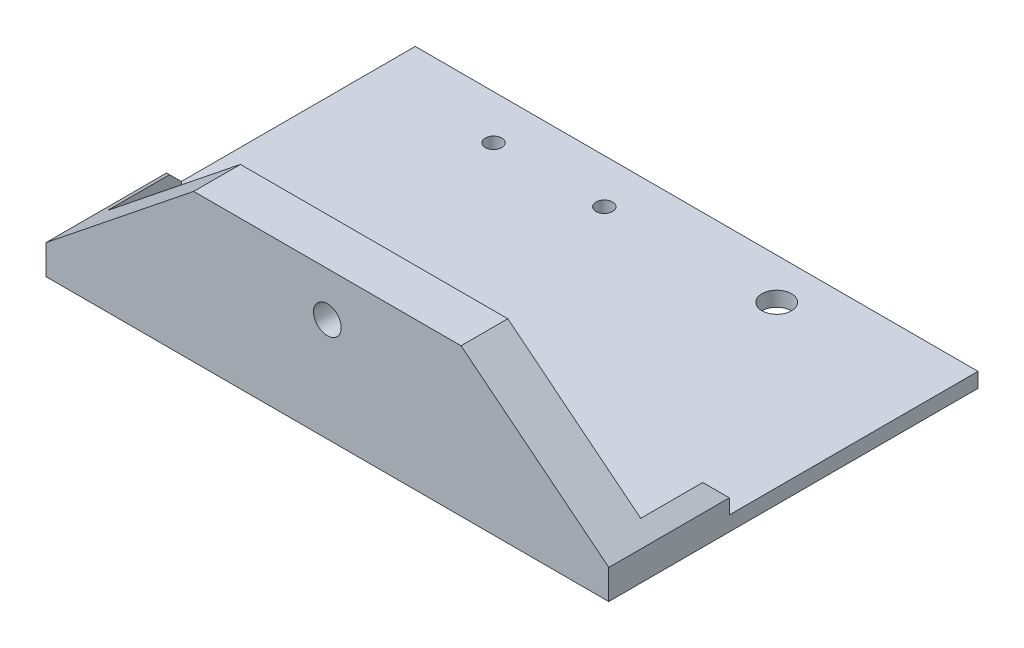
SolidWorks part; units mm, degrees
ref_plane "Front Plane" through (0, 0, 0) normal (0, 0, 1) x (1, 0, 0)
ref_plane "Top Plane" through (0, 0, 0) normal (0, 1, 0) x (1, 0, 0)
ref_plane "Right Plane" through (0, 0, 0) normal (1, 0, 0) x (0, 0, -1)
sketch "Sketch1" plane through (0, 0, 0) normal (0, 1, 0) x (1, 0, 0)
  line L9 (-4.893, 40.3981) -> (64.957, 40.3981)
  line L10 (-4.893, 40.3981) -> (-4.893, -23.1019)
  line L11 (-4.893, -23.1019) -> (64.957, -23.1019)
  line L12 (64.957, 40.3981) -> (64.957, -23.1019)
  circle A0 centre (2.727, 32.7781) radius 1.4224
  circle A2 centre (21.777, 32.7781) radius 1.4224
  circle A3 centre (2.727, 1.0281) radius 1.4224
  circle A4 centre (21.777, 1.0281) radius 1.4224
  circle A5 centre (49.6808, -9.8023) radius 2.54
  circle A6 centre (50.8255, 33.3777) radius 2.54
  point P4 (43.6232, 32.7781)
  point P5 (45.3849, -7.0434)
  point P6 (0, 0)
  point P7 (42.8096, -7.7431)
  point P8 (0, 0)
  point P13 (50.8255, 32.7781)
  point P14 (50.8255, -14.465)
  point P17 (49.6808, -14.8823)
  dimension "D9" = 7.62
  dimension "D10" = 7.62
  dimension "D11" = 2.8448
  dimension "D12" = 2.8448
  dimension "D1" = 5.08
  dimension "D2" = 5.08
  dimension "D13" = 2.8448
  dimension "D14" = 2.8448
  dimension "D3" = 31.75
  dimension "D4" = 19.05
  dimension "D5" = 31.75
  dimension "D6" = 63.5
  dimension "D7" = 69.85
  dimension "D8" = 19.05
  dimension "D15" = 43.18
extrude "Boss-Extrude1" add sketch "Sketch1" along normal blind 2.54 and the other way blind 2.54
sketch "Sketch2" plane through (0, 2.54, 0) normal (0, 1, 0) x (1, 0, 0)
  line L0 (64.957, -23.1019) -> (64.957, 40.3981) construction
  line L2 (-4.893, -23.1019) -> (64.957, -23.1019)
  line L3 (-4.893, -23.1019) -> (-4.893, -15.0633)
  line L4 (-4.893, -15.0633) -> (64.957, -15.0633)
  line L5 (64.957, -23.1019) -> (64.957, -15.0633)
extrude "Boss-Extrude2" add sketch "Sketch2" along normal blind 20.32
sketch "Sketch3" plane through (-4.893, 0, 0) normal (-1, 0, 0) x (0, 0, 1)
  line L0 (15.0633, 15.24) -> (2.3633, 2.54)
  line L6 (-40.3981, -2.54) -> (23.1019, -2.54)
  line L7 (23.1019, -2.54) -> (23.1019, 22.86)
  line L8 (23.1019, 22.86) -> (15.0633, 22.86)
  line L9 (15.0633, 22.86) -> (15.0633, 2.54)
  line L10 (15.0633, 2.54) -> (-40.3981, 2.54)
  line L11 (-40.3981, 2.54) -> (-40.3981, -2.54)
  line L12 (-40.3981, -2.54) -> (23.1019, -2.54)
  line L13 (23.1019, -2.54) -> (23.1019, 22.86)
  line L14 (23.1019, 22.86) -> (15.0633, 22.86)
  line L15 (15.0633, 22.86) -> (15.0633, 15.24)
  line L16 (2.3633, 2.54) -> (-40.3981, 2.54)
  line L17 (-40.3981, 2.54) -> (-40.3981, -2.54)
  dimension "D2" = 12.7
  dimension "D3" = 12.7
  dimension "D1" = 0
extrude "Boss-Extrude3" add sketch "Sketch3" along normal blind 2.54
sketch "Sketch4" plane through (64.957, 0, 0) normal (1, 0, 0) x (0, 0, -1)
  line L0 (-15.0633, 15.24) -> (-2.3633, 2.54) construction
  line L1 (-15.0633, 15.24) -> (-2.3633, 2.54)
  line L6 (-23.1019, -2.54) -> (40.3981, -2.54)
  line L7 (40.3981, -2.54) -> (40.3981, 2.54)
  line L8 (40.3981, 2.54) -> (-15.0633, 2.54)
  line L9 (-15.0633, 2.54) -> (-15.0633, 22.86)
  line L10 (-15.0633, 22.86) -> (-23.1019, 22.86)
  line L11 (-23.1019, 22.86) -> (-23.1019, -2.54)
  line L12 (-23.1019, -2.54) -> (40.3981, -2.54)
  line L13 (40.3981, -2.54) -> (40.3981, 2.54)
  line L14 (40.3981, 2.54) -> (-2.3633, 2.54)
  line L15 (-15.0633, 15.24) -> (-15.0633, 22.86)
  line L16 (-15.0633, 22.86) -> (-23.1019, 22.86)
  line L17 (-23.1019, 22.86) -> (-23.1019, -2.54)
  dimension "D1" = 0
extrude "Boss-Extrude4" add sketch "Sketch4" along normal blind 2.54
sketch "Sketch5" plane through (-7.433, 0, 0) normal (-1, 0, 0) x (0, 0, 1)
  line L0 (-40.3981, 2.54) -> (2.3633, 2.54)
  line L1 (2.3633, 2.54) -> (2.3633, 0)
  line L2 (2.3633, 0) -> (-40.3981, 0)
  line L3 (-40.3981, 2.54) -> (-40.3981, -2.54) construction
  line L4 (-40.3981, 0) -> (-40.3981, 2.54)
extrude "Cut-Extrude1" cut sketch "Sketch5" against normal through all
sketch "Sketch6" plane through (0, 0, 2.3633) normal (0, 0, -1) x (-1, 0, 0)
  line L0 (-67.497, 0) -> (7.433, 0) construction
  line L1 (-64.957, 2.54) -> (4.893, 2.54)
  line L2 (-64.957, 2.54) -> (-64.957, 0)
  line L3 (-64.957, 0) -> (4.893, 0)
  line L4 (4.893, 2.54) -> (4.893, 0)
extrude "Boss-Extrude5" add sketch "Sketch6" against normal up to surface (12.7 mm away) up to face at (30.032, 13.97, 15.0633)
sketch "Sketch7" plane through (0, 0, 2.3633) normal (0, 0, -1) x (-1, 0, 0)
  line L0 (-67.497, 0) -> (7.433, 0) construction
  line L1 (-64.957, 2.54) -> (4.893, 2.54)
  line L2 (-64.957, 2.54) -> (-64.957, 0)
  line L3 (-64.957, 0) -> (4.893, 0)
  line L4 (4.893, 2.54) -> (4.893, 0)
extrude "Cut-Extrude2" cut sketch "Sketch7" against normal blind 12.7
sketch "Sketch8" plane through (0, 0, 23.1019) normal (0, 0, 1) x (1, 0, 0)
  line L0 (-7.433, -2.54) -> (67.497, -2.54) construction
  line L2 (-7.433, -2.54) -> (-7.433, 22.86) construction
  circle A0 centre (30.032, 15.24) radius 2.3812
  dimension "D1" = 4.7625
  dimension "D2" = 17.78
  dimension "D3" = 37.465
extrude "Cut-Extrude3" cut sketch "Sketch8" against normal through all
sketch "Sketch9" plane through (67.497, 0, 0) normal (1, 0, 0) x (0, 0, -1)
  line L8 (-2.3633, 0) -> (-2.3633, 2.54)
  line L9 (-2.3633, 2.54) -> (-15.0633, 15.24)
  line L10 (-15.0633, 15.24) -> (-15.0633, 22.86)
  line L11 (-15.0633, 22.86) -> (-23.1019, 22.86)
  line L12 (-23.1019, 22.86) -> (-23.1019, -2.54)
  line L13 (-23.1019, -2.54) -> (40.3981, -2.54)
  line L14 (40.3981, -2.54) -> (40.3981, 0)
  line L15 (40.3981, 0) -> (-2.3633, 0)
  line L16 (-2.3633, 0) -> (-2.3633, 2.54)
  line L17 (-2.3633, 2.54) -> (-15.0633, 15.24)
  line L18 (-15.0633, 15.24) -> (-15.0633, 22.86)
  line L19 (-15.0633, 22.86) -> (-23.1019, 22.86)
  line L20 (-23.1019, 22.86) -> (-23.1019, -2.54)
  line L21 (-23.1019, -2.54) -> (40.3981, -2.54)
  line L22 (40.3981, -2.54) -> (40.3981, 0)
  line L23 (40.3981, 0) -> (-2.3633, 0)
  dimension "D1" = 0
extrude "Boss-Extrude6" add sketch "Sketch9" along normal blind 10.922
sketch "Sketch10" plane through (-7.433, 0, 0) normal (-1, 0, 0) x (0, 0, 1)
  line L8 (2.3633, 2.54) -> (2.3633, 0)
  line L9 (2.3633, 0) -> (-40.3981, 0)
  line L10 (-40.3981, 0) -> (-40.3981, -2.54)
  line L11 (-40.3981, -2.54) -> (23.1019, -2.54)
  line L12 (23.1019, -2.54) -> (23.1019, 22.86)
  line L13 (23.1019, 22.86) -> (15.0633, 22.86)
  line L14 (15.0633, 22.86) -> (15.0633, 15.24)
  line L15 (15.0633, 15.24) -> (2.3633, 2.54)
  line L16 (2.3633, 2.54) -> (2.3633, 0)
  line L17 (2.3633, 0) -> (-40.3981, 0)
  line L18 (-40.3981, 0) -> (-40.3981, -2.54)
  line L19 (-40.3981, -2.54) -> (23.1019, -2.54)
  line L20 (23.1019, -2.54) -> (23.1019, 22.86)
  line L21 (23.1019, 22.86) -> (15.0633, 22.86)
  line L22 (15.0633, 22.86) -> (15.0633, 15.24)
  line L23 (15.0633, 15.24) -> (2.3633, 2.54)
  dimension "D1" = 0
extrude "Boss-Extrude7" add sketch "Sketch10" along normal blind 10.922
sketch "Sketch12" plane through (64.957, 0, 0) normal (-1, 0, 0) x (0, 0, 1)
  line L4 (15.0633, 15.24) -> (2.3633, 2.54)
  line L5 (2.3633, 2.54) -> (2.3633, 0)
  line L6 (2.3633, 0) -> (15.0633, 0)
  line L7 (15.0633, 0) -> (15.0633, 15.24)
  line L8 (15.0633, 15.24) -> (2.3633, 2.54)
  line L9 (2.3633, 2.54) -> (2.3633, 0)
  line L10 (2.3633, 0) -> (15.0633, 0)
  line L11 (15.0633, 0) -> (15.0633, 15.24)
  dimension "D1" = 0
extrude "Cut-Extrude4" cut sketch "Sketch12" against normal blind 10.922
sketch "Sketch13" plane through (-4.893, 0, 0) normal (1, 0, 0) x (0, 0, -1)
  line L4 (-2.3633, 2.54) -> (-15.0633, 15.24)
  line L5 (-15.0633, 15.24) -> (-15.0633, 0)
  line L6 (-15.0633, 0) -> (-2.3633, 0)
  line L7 (-2.3633, 0) -> (-2.3633, 2.54)
  line L8 (-2.3633, 2.54) -> (-15.0633, 15.24)
  line L9 (-15.0633, 15.24) -> (-15.0633, 0)
  line L10 (-15.0633, 0) -> (-2.3633, 0)
  line L11 (-2.3633, 0) -> (-2.3633, 2.54)
  dimension "D1" = 0
extrude "Cut-Extrude5" cut sketch "Sketch13" against normal blind 10.922
sketch "Sketch14" plane through (0, 0, 23.1019) normal (0, 0, 1) x (1, 0, 0)
  line L0 (78.419, 22.86) -> (53.019, 22.86)
  line L1 (-18.355, 22.86) -> (78.419, 22.86) construction
  line L2 (53.019, 22.86) -> (78.419, 2.54)
  line L3 (78.419, 22.86) -> (78.419, -2.54) construction
  line L4 (78.419, 2.54) -> (78.419, 22.86)
  line L5 (-18.355, 22.86) -> (7.045, 22.86)
  line L6 (7.045, 22.86) -> (-18.355, 2.54)
  line L7 (-18.355, -2.54) -> (-18.355, 22.86) construction
  line L8 (-18.355, 2.54) -> (-18.355, 22.86)
  dimension "D1" = 25.4
  dimension "D2" = 20.32
  dimension "D3" = 25.4
  dimension "D4" = 20.32
extrude "Cut-Extrude6" cut sketch "Sketch14" against normal through all both and the other way through all
